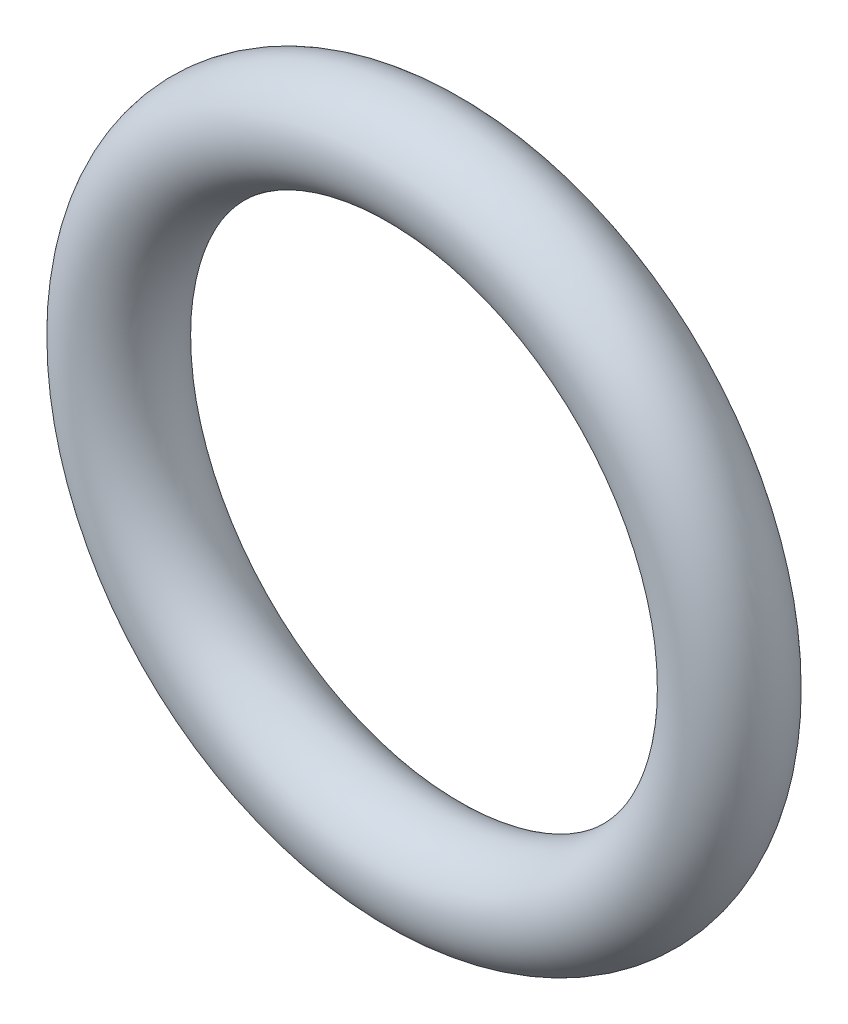
SolidWorks part; units mm, degrees
material "Rubber"
ref_plane "Front Plane" through (0, 0, 0) normal (0, 0, 1) x (1, 0, 0)
ref_plane "Top Plane" through (0, 0, 0) normal (0, 1, 0) x (1, 0, 0)
ref_plane "Right Plane" through (0, 0, 0) normal (1, 0, 0) x (0, 0, -1)
sketch "Sketch1" plane through (0, 0, 0) normal (1, 0, 0) x (0, 0, -1)
  line L0 (-24.2644, 0) -> (26.1006, 0) construction
  circle A0 centre (0, 6) radius 1
  dimension "D2" = 2
  dimension "D1" = 6
revolve "Revolve1" add sketch "Sketch1" angle 360 about L0
ref_axis "Axis1" through (0, 0, -0.55) along (0, 0, 1)
